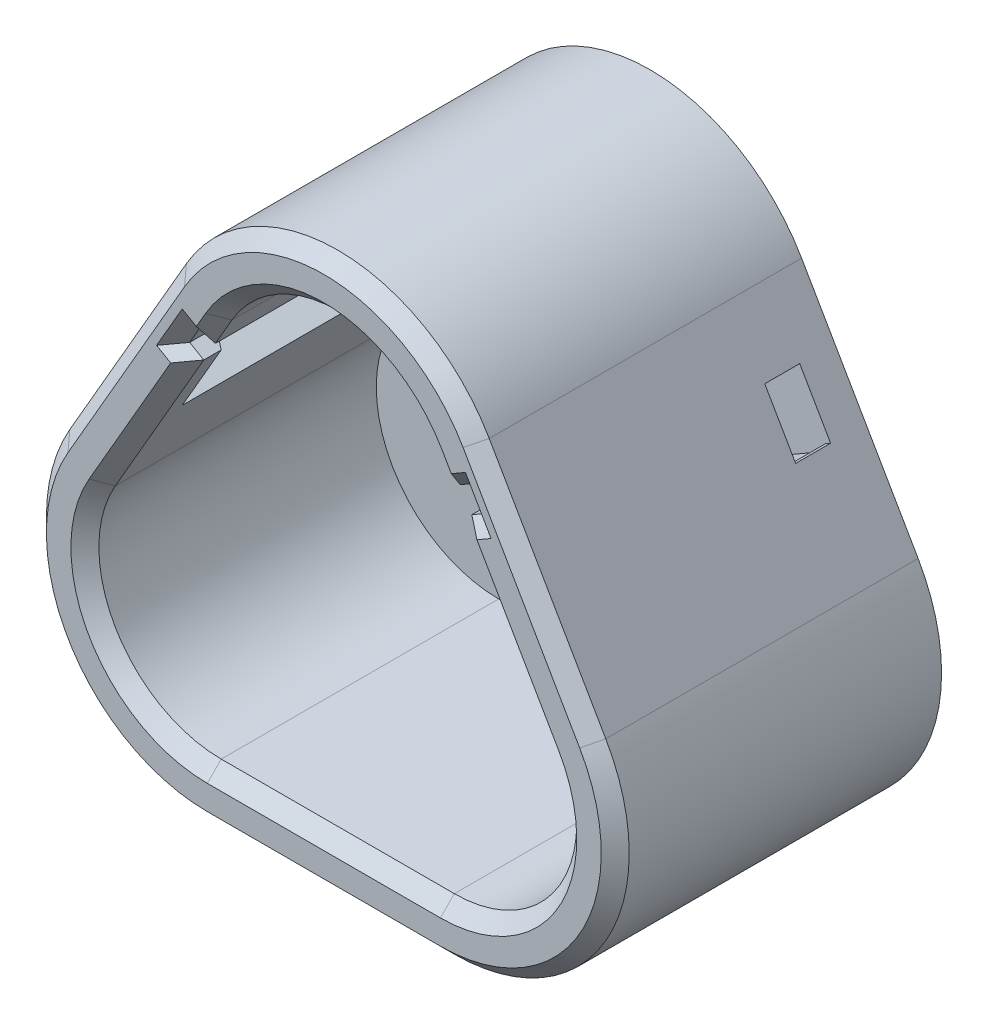
SolidWorks part; units mm, degrees
ref_plane "Plan de face" through (0, 0, 0) normal (0, 0, 1) x (1, 0, 0)
ref_plane "Plan de dessus" through (0, 0, 0) normal (0, 1, 0) x (1, 0, 0)
ref_plane "Plan de droite" through (0, 0, 0) normal (1, 0, 0) x (0, 0, -1)
sketch "Esquisse1" plane through (0, 0, 0) normal (0, 0, 1) x (1, 0, 0)
  line L0 (-18.6603, -0.7735) -> (-8.6603, 16.547)
  line L1 (8.6603, 16.547) -> (18.6603, -0.7735)
  line L2 (-10, -15.7735) -> (10, -15.7735)
  line L3 (0, -15.7735) -> (0, 0) construction
  line L4 (-13.6603, 7.8868) -> (0, 0) construction
  line L5 (13.6603, 7.8868) -> (0, 0) construction
  line L6 (-20, 4.9198) -> (-20, -15.8947) construction
  line L7 (20, 16.147) -> (20, -7.4428) construction
  line L8 (-22.9904, 1.7265) -> (-12.9904, 19.047)
  line L9 (12.9904, 19.047) -> (22.9904, 1.7265)
  line L10 (-10, -20.7735) -> (10, -20.7735)
  arc A0 (-18.6603, -0.7735) -> (-10, -15.7735) centre (-10, -5.7735) ccw
  arc A1 (8.6603, 16.547) -> (-8.6603, 16.547) centre (0, 11.547) ccw
  arc A2 (18.6603, -0.7735) -> (10, -15.7735) centre (10, -5.7735) cw
  arc A3 (12.9904, 19.047) -> (-12.9904, 19.047) centre (0, 11.547) ccw
  arc A4 (22.9904, 1.7265) -> (10, -20.7735) centre (10, -5.7735) cw
  arc A5 (-22.9904, 1.7265) -> (-10, -20.7735) centre (-10, -5.7735) ccw
  point P18 (-20, -5.7735)
  point P19 (0, 21.547)
  point P21 (20, -5.7735)
  dimension "D1" = 10
  dimension "D2" = 40
  dimension "D3" = 5
extrude "Boss.-Extru.1" add sketch "Esquisse1" along normal blind 25
sketch "Esquisse2" plane through (0, 0, 25) normal (0, 0, 1) x (1, 0, 0)
  line L0 (-10.9144, 12.6428) -> (-12.3, 13.4428)
  line L1 (-8.6603, 16.547) -> (-18.6603, -0.7735) construction
  line L2 (-12.3, 13.4428) -> (-11.6, 14.6552)
  line L3 (-11.6, 14.6552) -> (-10.2144, 13.8552)
  line L4 (-10.9144, 12.6428) -> (-10.2144, 13.8552)
  line L5 (10.2144, 13.8552) -> (11.6, 14.6552)
  line L6 (18.6603, -0.7735) -> (8.6603, 16.547) construction
  line L7 (11.6, 14.6552) -> (12.3, 13.4428)
  line L8 (12.3, 13.4428) -> (10.9144, 12.6428)
  line L9 (10.9144, 12.6428) -> (10.2144, 13.8552)
  dimension "D1" = 1.4
  dimension "D2" = 1.6
  dimension "D3" = 24.6
extrude "Enlèv. mat.-Extru.1" cut sketch "Esquisse2" against normal blind 20
sketch "Esquisse3" plane through (0, 0, 25) normal (0, 0, 1) x (1, 0, 0)
  line L0 (-10.0644, 14.115) -> (-11.7098, 15.065)
  line L1 (-8.6603, 16.547) -> (-10.2144, 13.8552) construction
  line L2 (-11.7098, 15.065) -> (-12.7098, 13.333)
  line L3 (-12.7098, 13.333) -> (-11.0644, 12.383)
  line L4 (-10.9144, 12.6428) -> (-18.6603, -0.7735) construction
  line L5 (-11.0644, 12.383) -> (-10.0644, 14.115)
  line L6 (-10.2144, 13.8552) -> (-11.6, 14.6552) construction
  line L7 (-11.6, 14.6552) -> (-12.3, 13.4428) construction
  line L8 (-12.3, 13.4428) -> (-10.9144, 12.6428) construction
  dimension "D1" = 0.3
  dimension "D2" = 0.3
  dimension "D3" = 0.3
extrude "Enlèv. mat.-Extru.2" cut sketch "Esquisse3" against normal through all contours L2 L3 L5 L0
mirror "Symétrie1" about plane through (0, 0, 0) normal (1, 0, 0) of "Enlèv. mat.-Extru.2"
sketch "Esquisse6" plane through (0, 0, 0) normal (0, 0, -1) x (-1, 0, 0)
  line L0 (11.25, 12.0614) -> (15.1471, 14.3114)
  line L1 (11.0644, 12.383) -> (18.6603, -0.7735) construction
  line L2 (15.1471, 14.3114) -> (18.2971, 8.8555)
  line L3 (18.2971, 8.8555) -> (14.4, 6.6055)
  line L4 (14.4, 6.6055) -> (11.25, 12.0614)
  line L5 (-11.25, 12.0614) -> (-15.1471, 14.3114)
  line L6 (-18.6603, -0.7735) -> (-11.0644, 12.383) construction
  line L7 (-15.1471, 14.3114) -> (-18.2971, 8.8555)
  line L8 (-18.2971, 8.8555) -> (-14.4, 6.6055)
  line L9 (-14.4, 6.6055) -> (-11.25, 12.0614)
  dimension "D1" = 22.5
  dimension "D2" = 6.3
  dimension "D3" = 4.5
extrude "Enlèv. mat.-Extru.4" cut sketch "Esquisse6" against normal blind 20
sketch "Esquisse5" plane through (0, 0, 25) normal (0, 0, 1) x (1, 0, 0)
  line L1 (-11.0644, 12.383) -> (-18.6603, -0.7735) construction
  line L2 (-10, -15.7735) -> (10, -15.7735) construction
  line L3 (18.6603, -0.7735) -> (11.0644, 12.383) construction
  line L8 (-8.6603, 16.547) -> (-10.0644, 14.115) construction
  line L9 (10.0644, 14.115) -> (8.6603, 16.547) construction
  line L14 (-8.6603, 16.547) -> (-10.0644, 14.115)
  line L15 (10.0644, 14.115) -> (8.6603, 16.547)
  line L19 (18.6603, -0.7735) -> (11.0644, 12.383)
  line L20 (-10, -15.7735) -> (10, -15.7735)
  line L21 (-11.0644, 12.383) -> (-18.6603, -0.7735)
  line L22 (-11.0644, 12.383) -> (-10.0644, 14.115)
  line L23 (11.0644, 12.383) -> (10.0644, 14.115)
  line L24 (-9.0933, 16.797) -> (-10.4974, 14.365)
  line L25 (-11.4974, 12.633) -> (-10.4974, 14.365)
  line L26 (-11.4974, 12.633) -> (-19.0933, -0.5235)
  line L27 (-10, -16.2735) -> (10, -16.2735)
  line L28 (19.0933, -0.5235) -> (11.4974, 12.633)
  line L29 (11.4974, 12.633) -> (10.4974, 14.365)
  line L30 (10.4974, 14.365) -> (9.0933, 16.797)
  arc A0 (-18.6603, -0.7735) -> (-10, -15.7735) centre (-10, -5.7735) ccw construction
  arc A1 (10, -15.7735) -> (18.6603, -0.7735) centre (10, -5.7735) ccw construction
  arc A2 (8.6603, 16.547) -> (-8.6603, 16.547) centre (0, 11.547) ccw construction
  arc A3 (8.6603, 16.547) -> (-8.6603, 16.547) centre (0, 11.547) ccw
  arc A4 (10, -15.7735) -> (18.6603, -0.7735) centre (10, -5.7735) ccw
  arc A5 (-18.6603, -0.7735) -> (-10, -15.7735) centre (-10, -5.7735) ccw
  arc A6 (-19.0933, -0.5235) -> (-10, -16.2735) centre (-10, -5.7735) ccw
  arc A7 (10, -16.2735) -> (19.0933, -0.5235) centre (10, -5.7735) ccw
  arc A8 (9.0933, 16.797) -> (-9.0933, 16.797) centre (0, 11.547) ccw
  dimension "D1" = 0.5
extrude "Enlèv. mat.-Extru.3" cut sketch "Esquisse5" against normal through all
chamfer "Chanfrein1" distance 1.2 angle 45 20 edges at (-11.1036, 14.715, 25) (-12.2098, 14.199, 25) (-12.1036, 12.983, 25) (12.1036, 12.983, 25) (12.2098, 14.199, 25) (11.1036, 14.715, 25) (-17.9904, 10.3868, 25) (0, 26.547, 25) (17.9904, 10.3868, 25) (22.9904, -13.2735, 25) (0, -20.7735, 25) (-22.9904, -13.2735, 25) (0, 22.047, 25) (-9.7953, 15.581, 25) (-15.2953, 6.0547, 25) (-19.0933, -11.0235, 25) (0, -16.2735, 25) (19.0933, -11.0235, 25) (15.2953, 6.0547, 25) (9.7953, 15.581, 25)
sketch "Esquisse4" plane through (0, 0, 0) normal (0, 0, -1) x (-1, 0, 0)
  line L3 (22.9904, 1.7265) -> (12.9904, 19.047)
  line L4 (-12.9904, 19.047) -> (-22.9904, 1.7265)
  line L5 (-10, -20.7735) -> (10, -20.7735)
  line L6 (22.9904, 1.7265) -> (12.9904, 19.047)
  line L7 (-12.9904, 19.047) -> (-22.9904, 1.7265)
  line L8 (-10, -20.7735) -> (10, -20.7735)
  arc A3 (10, -20.7735) -> (22.9904, 1.7265) centre (10, -5.7735) ccw
  arc A4 (12.9904, 19.047) -> (-12.9904, 19.047) centre (0, 11.547) ccw
  arc A5 (-22.9904, 1.7265) -> (-10, -20.7735) centre (-10, -5.7735) ccw
  arc A6 (10, -20.7735) -> (22.9904, 1.7265) centre (10, -5.7735) ccw
  arc A7 (12.9904, 19.047) -> (-12.9904, 19.047) centre (0, 11.547) ccw
  arc A8 (-22.9904, 1.7265) -> (-10, -20.7735) centre (-10, -5.7735) ccw
  dimension "D1" = 0
extrude "Boss.-Extru.2" add sketch "Esquisse4" along normal blind 3
sketch "Esquisse7" plane through (-2.5959, 4.4962, 0) normal (-0.5, 0.866, 0) x (0.866, 0.5, 0)
  line L0 (16.2735, -20) -> (17.6735, -20)
  line L1 (16.2735, -23.8) -> (16.2735, 0) construction
  line L2 (17.6735, -20) -> (17.6735, 0)
  line L3 (17.6735, 0) -> (16.2735, 0)
  line L4 (16.2735, 0) -> (16.2735, -20)
  line L5 (16.2735, -20) -> (20.2735, -20) construction
  line L6 (16.2735, -23.8) -> (17.6735, -23.8) construction
  line L7 (16.2735, 0) -> (20.2735, 0) construction
extrude "Enlèv. mat.-Extru.5" cut sketch "Esquisse7" against normal up to next
mirror "Symétrie2" about plane through (0, 0, 0) normal (1, 0, 0) of "Enlèv. mat.-Extru.5"
chamfer "Chanfrein2" distance 4 angle 30 1 edges at (13.1652, 9.7442, 20) first distance on face at (14.23, 11.5, 20)
sketch "Esquisse8" plane through (17.5574, 10.1368, 0) normal (-0.866, -0.5, 0) x (0, 0, 1)
  line L0 (0, 4.8205) -> (0, -1.4795) construction
  line L1 (3, 4.3205) -> (0, 4.3205)
  line L2 (3, 4.3205) -> (3, -0.9795)
  line L3 (3, -0.9795) -> (0, -0.9795)
  line L4 (0, 4.3205) -> (0, -0.9795)
  line L5 (20, -1.4795) -> (0, -1.4795) construction
  point P9 (0, 1.6705)
  dimension "D1" = 0.5
  dimension "D2" = 3
extrude "Enlèv. mat.-Extru.6" cut sketch "Esquisse8" against normal up to next
mirror "Symétrie3" about plane through (0, 0, 0) normal (1, 0, 0) of "Enlèv. mat.-Extru.6"
chamfer "Chanfrein3" distance 4 angle 30 1 edges at (-13.1652, 9.7442, 20) first distance on face at (-14.23, 11.5, 20)
hole_wizard "Fraisage pour vis à tête fraisée M51" positions "Esquisse9" profile "Esquisse10" countersink size "M5" standard "ISO" end condition up to next
sketch "Esquisse9" plane through (0, 0, 0) normal (0, 0, 1) x (1, 0, 0)
  point P0 (0, 0)
sketch "Esquisse10" plane through (0, 0, 0) normal (1, 0, 0) x (0, -1, 0)
  line L0 (0, 0) -> (0, 3)
  line L1 (0, 3) -> (2.75, 3)
  line L2 (2.75, 3) -> (2.75, 2.45)
  line L3 (2.75, 2.45) -> (5.2, 0)
  line L5 (5.2, 0) -> (0, 0)
  line L6 (-2.75, 2.45) -> (-5.2, 0) construction
  line L11 (0, -6.35) -> (0, 107.95) construction
  dimension "Diamètre du perçage jusqu'au prochain" = 5.5
  dimension "Profondeur du perçage jusqu'au prochain" = 3
  dimension "Diamètre du fraisage entrant" = 10.4
  dimension "Angle du fraisage entrant" = 90
